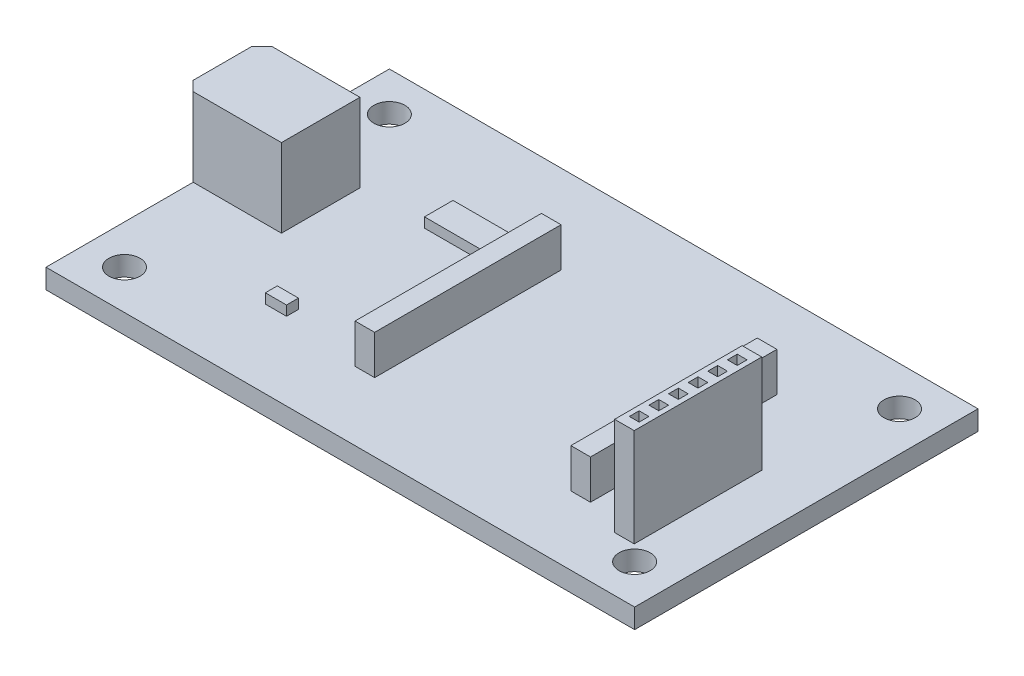
SolidWorks part; units mm, degrees
ref_plane "Front" through (0, 0, 0) normal (0, 0, 1) x (1, 0, 0)
ref_plane "Top" through (0, 0, 0) normal (0, 1, 0) x (1, 0, 0)
ref_plane "Right" through (0, 0, 0) normal (1, 0, 0) x (0, 0, -1)
sketch "Sketch1" plane through (0, 0, 0) normal (0, 1, 0) x (1, 0, 0)
  line L0 (0, 35) -> (0, 0)
  line L1 (0, 0) -> (60, 0)
  line L2 (4, 4) -> (4, 31) construction
  line L3 (0, 35) -> (60, 35)
  line L4 (60, 0) -> (60, 35)
  line L5 (4, 4) -> (56, 4) construction
  line L6 (56, 4) -> (56, 31) construction
  line L7 (56, 31) -> (4, 31) construction
  circle A0 centre (4, 4) radius 1.5875
  circle A1 centre (4, 31) radius 1.5875
  circle A2 centre (56, 31) radius 1.5875
  circle A3 centre (56, 4) radius 1.5875
  dimension "D1" = 35
  dimension "D3" = 4
  dimension "D4" = 4
  dimension "D5" = 31
  dimension "D6" = 3.175
  dimension "D2" = 60
  dimension "D7" = 52
extrude "Boss-Extrude1" add sketch "Sketch1" along normal blind 2
sketch "Sketch2" plane through (0, 2, 0) normal (0, 1, 0) x (1, 0, 0)
  line L0 (24.5, 26) -> (26.5, 26)
  line L1 (24.5, 26) -> (24.5, 7)
  line L2 (24.5, 7) -> (26.5, 7)
  line L3 (26.5, 26) -> (26.5, 7)
  line L4 (46.5, 26) -> (46.5, 7)
  line L5 (48.5, 7) -> (46.5, 7)
  line L6 (48.5, 26) -> (48.5, 7)
  line L7 (48.5, 26) -> (46.5, 26)
extrude "Boss-Extrude2" add sketch "Sketch2" along normal blind 4
sketch "Sketch3" plane through (0, 2, 0) normal (0, 1, 0) x (1, 0, 0)
  line L1 (54.4052, 5.5533) -> (52.4052, 5.5533)
  line L2 (54.4052, 5.5533) -> (54.4052, 18.5533)
  line L3 (54.4052, 18.5533) -> (52.4052, 18.5533)
  line L4 (52.4052, 5.5533) -> (52.4052, 18.5533)
extrude "Boss-Extrude3" add sketch "Sketch3" along normal blind 10
sketch "Sketch4" plane through (0, 2, 0) normal (0, 1, 0) x (1, 0, 0)
  line L1 (15.843, 25.6412) -> (21.7496, 25.6412)
  line L2 (15.843, 25.6412) -> (15.843, 22.7348)
  line L3 (15.843, 22.7348) -> (21.7496, 22.7348)
  line L4 (21.7496, 25.6412) -> (21.7496, 22.7348)
  line L5 (14.4367, 9.1403) -> (16.593, 9.1403)
  line L6 (14.4367, 9.1403) -> (14.4367, 7.9215)
  line L7 (14.4367, 7.9215) -> (16.593, 7.9215)
  line L8 (16.593, 9.1403) -> (16.593, 7.9215)
extrude "Boss-Extrude4" add sketch "Sketch4" along normal blind 1
sketch "Sketch6" plane through (0, 2, 0) normal (0, 1, 0) x (1, 0, 0)
  line L1 (9, 23) -> (9, 15)
  line L2 (9, 23) -> (0, 23)
  line L3 (-1, 22) -> (-1, 16)
  line L4 (9, 15) -> (0, 15)
  line L14 (0, 23) -> (-1, 22)
  line L15 (0, 15) -> (-1, 16)
extrude "Boss-Extrude5" add sketch "Sketch6" along normal blind 8
sketch "Sketch7" plane through (-1, 0, 0) normal (-1, 0, 0) x (0, 0, 1)
  line L0 (-20.5, 9.25) -> (-17.5, 9.25)
  line L1 (-20.5, 9.25) -> (-20.5, 6.25)
  line L2 (-20.5, 6.25) -> (-17.5, 6.25)
  line L3 (-17.5, 9.25) -> (-17.5, 6.25)
  line L4 (-20.5, 5.75) -> (-20.5, 2.75)
  line L5 (-20.5, 5.75) -> (-17.5, 5.75)
  line L6 (-17.5, 5.75) -> (-17.5, 2.75)
  line L7 (-20.5, 2.75) -> (-17.5, 2.75)
extrude "Cut-Extrude1" cut sketch "Sketch7" against normal blind 9
sketch "Sketch9" plane through (0, 12, 0) normal (0, 1, 0) x (1, 0, 0)
  line L0 (52.9052, 13.5533) -> (53.9052, 13.5533)
  line L1 (52.9052, 17.5533) -> (53.9052, 17.5533)
  line L2 (52.9052, 17.5533) -> (52.9052, 16.5533)
  line L3 (52.9052, 16.5533) -> (53.9052, 16.5533)
  line L4 (53.9052, 17.5533) -> (53.9052, 16.5533)
  line L6 (52.9052, 15.5533) -> (53.9052, 15.5533)
  line L8 (52.9052, 15.5533) -> (52.9052, 14.5533)
  line L9 (52.9052, 14.5533) -> (53.9052, 14.5533)
  line L10 (53.9052, 15.5533) -> (53.9052, 14.5533)
  line L11 (52.9052, 12.5533) -> (53.9052, 12.5533)
  line L12 (52.9052, 13.5533) -> (52.9052, 12.5533)
  line L13 (53.9052, 13.5533) -> (53.9052, 12.5533)
  line L14 (52.9052, 11.5533) -> (52.9052, 10.5533)
  line L15 (52.9052, 10.5533) -> (53.9052, 10.5533)
  line L16 (52.9052, 9.5533) -> (52.9052, 8.5533)
  line L17 (52.9052, 9.5533) -> (53.9052, 9.5533)
  line L19 (52.9052, 11.5533) -> (53.9052, 11.5533)
  line L20 (53.9052, 9.5533) -> (53.9052, 8.5533)
  line L22 (53.9052, 11.5533) -> (53.9052, 10.5533)
  line L23 (52.9052, 8.5533) -> (53.9052, 8.5533)
  line L24 (52.9052, 6.5533) -> (53.9052, 6.5533)
  line L25 (52.9052, 7.5533) -> (53.9052, 7.5533)
  line L27 (52.9052, 7.5533) -> (52.9052, 6.5533)
  line L28 (53.9052, 7.5533) -> (53.9052, 6.5533)
extrude "Cut-Extrude2" cut sketch "Sketch9" against normal blind 9
